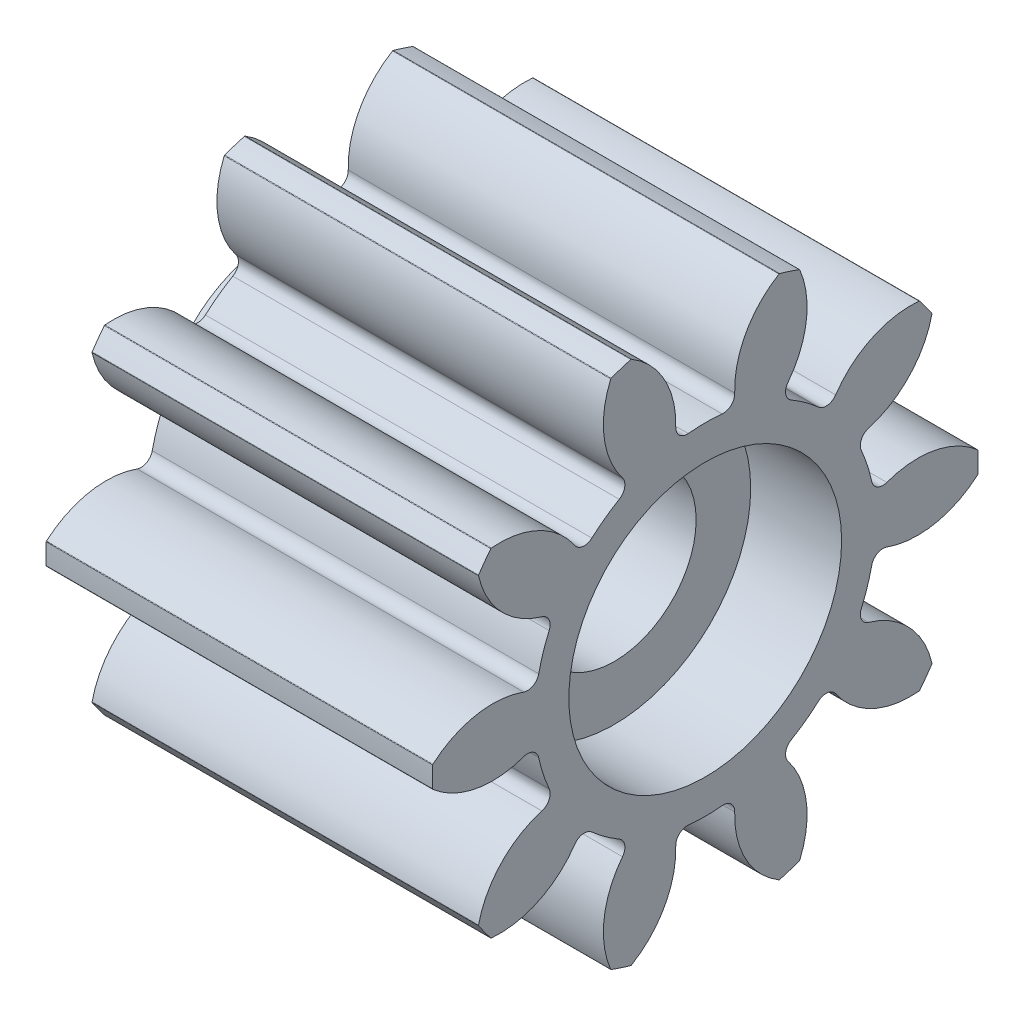
SolidWorks part; units mm, degrees
ref_plane "Plane1" through (0, 0, 0) normal (0, 0, 1) x (1, 0, 0)
ref_plane "Plane2" through (0, 0, 0) normal (0, 1, 0) x (1, 0, 0)
ref_plane "Plane3" through (0, 0, 0) normal (1, 0, 0) x (0, 0, -1)
sketch "HoldingSke" plane through (0, 0, 0) normal (0, 1, 0) x (1, 0, 0)
  line L0 (0, 0) -> (0.9848, -0.1736)
  line L1 (-15, 0) -> (100, 0) construction
  line L2 (0, 0) -> (-2.1039, 2.3779)
  line L3 (0, 0) -> (-11.863, 4.5341)
  line L4 (0, 0) -> (8.5048, 1.4996)
  line L5 (0, 0) -> (-46.8476, -17.4728)
  line L6 (0, 0) -> (-8.2896, -5.593)
  line L7 (-2.1039, 2.3779) -> (8.6586, 51.2059)
  line L8 (-76.2, 54.61) -> (-75.7, 54.61)
  line L9 (-67.7845, 28.3722) -> (-49.3413, 33.142)
  line L10 (-76.2, 71.12) -> (104.1128, 71.12)
  line L11 (0, 0) -> (-10, 0)
  line L12 (-76.2, 101.6) -> (-76.162, 101.6)
  line L13 (24.9733, 27.94) -> (52.9518, 28.4284)
  line L14 (24.9733, 27.94) -> (24.9743, 27.94)
  line L15 (24.9733, 27.94) -> (100.4006, 29.5858)
  line L16 (-63.627, -1) -> (-12.827, -1)
  circle A0 centre (0, 0) radius 1.5
  circle A1 centre (0, 0) radius 3.749
  circle A2 centre (0, 0) radius 37.5
  circle A3 centre (0, 0) radius 1.5
  dimension "Num_teeth" = 10
  dimension "Pitch_radius" = 180.3128
  dimension "Width" = 10
sketch "BasProSke" plane through (0, 0, 0) normal (0, 1, 0) x (1, 0, 0)
  line L0 (-10, 0) -> (60, 0) construction
  line L1 (0, 0) -> (0, 6)
  line L2 (0, 0) -> (8.5, 0)
  line L3 (8.5, 0) -> (8.5, 6)
  line L4 (8.5, 6) -> (0, 6)
  dimension "Thickness" = 8.5
  dimension "Diameter" = 12
revolve "Base-Revolve" add sketch "BasProSke" angle 360 about L0
sketch "TooCutSke" plane through (0, 0, 0) normal (1, 0, 0) x (0, 0, -1)
  line L1 (0, 0) -> (0, 107) construction
  line L2 (0, 0) -> (-0.8485, 4.9275) construction
  line L3 (0, 0) -> (-3.0584, 9.4126) construction
  line L4 (-0.8485, 4.9275) -> (-1.5292, 4.7063) construction
  arc A0 (0.6809, 3.6866) -> (-0.6809, 3.6866) centre (0, 0) ccw
  arc A1 (1.66, 5.7922) -> (-1.66, 5.7922) centre (0, 0) ccw
  circle A2 centre (0, 0) radius 5 construction
  circle A3 centre (0, 0) radius 4.8407 construction
  arc A4 (-0.6809, 3.6866) -> (-1.66, 5.7922) centre (-2.6471, 4.0528) ccw
  arc A5 (1.66, 5.7922) -> (0.6809, 3.6866) centre (2.6471, 4.0528) ccw
extrude "ToothCut" cut sketch "TooCutSke" along normal through all
fillet "Breaks" radius 0.02 2 edges at (4.25, 5.7745, -1.6294) (4.25, 5.7745, 1.6294) tangent propagation no
fillet "RootFillets" radius 0.251 2 edges at (4.25, 3.6866, -0.6809) (4.25, 3.6866, 0.6809)
pattern_circular "TeethCuts" count 10 every 36 about axis through (-10, 0, 0) along (1, 0, 0) of "ToothCut", "RootFillets", "Breaks"
sketch "HubNeaOneSke" plane through (0, 0, 0) normal (-1, 0, 0) x (0, 0, 1)
  circle A0 centre (0, 0) radius 3.749
  dimension "Diameter" = 7.498
extrude "HubNearOne" [suppressed] add sketch "HubNeaOneSke" along normal blind 41.5001
sketch "HubNeaBotSke" plane through (0, 0, 0) normal (-1, 0, 0) x (0, 0, 1)
  circle A0 centre (0, 0) radius 3.749
  dimension "Diameter" = 7.498
extrude "HubNearBoth" [suppressed] add sketch "HubNeaBotSke" along normal blind 20.75
ref_plane "FarPln" through (8.5, 0, 0) normal (1, 0, 0) x (0, 0, -1)
sketch "HubFarSke" plane through (8.5, 0, 0) normal (1, 0, 0) x (0, 0, -1)
  circle A0 centre (0, 0) radius 3.749
  dimension "Diameter" = 7.498
extrude "HubFar" [suppressed] add sketch "HubFarSke" along normal blind 20.75
sketch "BorSke" plane through (0, 0, 0) normal (1, 0, 0) x (0, 0, -1)
  circle A0 centre (0, 0) radius 1.8
  dimension "Diameter" = 3.6
extrude "Bore" cut sketch "BorSke" along normal mid plane 100.0001
sketch "KeySke" plane through (0, 0, 0) normal (1, 0, 0) x (0, 0, -1)
  line L0 (-0.6, 0) -> (-0.6, 2)
  line L1 (-0.6, 2) -> (0.6, 2)
  line L2 (0.6, 2) -> (0.6, 0)
  line L3 (0, 0) -> (0, 34) construction
  line L4 (-0.6, 0) -> (0.6, 0)
  dimension "Width" = 1.2
extrude "Keyway" [suppressed] cut sketch "KeySke" along normal mid plane 100.0001
pattern_circular "Keyway2" [suppressed] count 2 every 90 about axis through (-10, 0, 0) along (1, 0, 0) reverse direction yes
sketch "Sketch3" plane through (0, 0, 0) normal (-1, 0, 0) x (0, 0, 1)
  circle A0 centre (0, 0) radius 2.5
  circle A1 centre (0, 0) radius 1.8 construction
  circle A2 centre (0, 0) radius 1.8
  dimension "D1" = 5
extrude "Boss-Extrude1" add sketch "Sketch3" along normal blind 1
sketch "Sketch4" plane through (8.5, 0, 0) normal (1, 0, 0) x (0, 0, -1)
  circle A0 centre (0, 0) radius 3
  dimension "D1" = 6
extrude "Cut-Extrude2" cut sketch "Sketch4" against normal blind 2
equation "' \"Module@HoldingSke\" = 6.35"
equation "' \"Num_teeth@HoldingSke\" = 12"
equation "' \"Ap@HoldingSke\" =  20"
equation "' \"Ap@HoldingSke\" = 20"
equation "' \"Width@HoldingSke\" = 0.5 * 25.4"
equation "' \"Hub_dia@HoldingSke\"= 1 * 25.4"
equation "' \"Hub_dia@HoldingSke\" = 1 * 25.4"
equation "' \"Overall_len@HoldingSke\" = 1.0 * 25.4"
equation "' \"Bore@HoldingSke\" = 0.75 * 25.4"
equation "' \"T_dim@HoldingSke\" = 0.1 * 25.4"
equation "' \"Width@KeySke\" = 0.25 * 25.4"
equation "' \"Show_teeth@HoldingSke\" = 13"
equation "' \"Backlash@HoldingSke\" = 0.009 * 25.4"
equation "' \"Addendum_fac@HoldingSke\" = 1.0"
equation "' \"Dedendum_fac@HoldingSke\" = 1.25"
equation "' \"Dedendum_add@HoldingSke\" = 0.00005 * 25.4"
equation "' \"Clearance_fac@HoldingSke\" = 0.25"
equation "\"Pitch@HoldingSke\" = 1 / \"Module@HoldingSke\""
equation "\"Overcut_dia@TooCutSke\" = (\"Num_teeth@HoldingSke\" + 2 * \"Addendum_fac@HoldingSke\") / \"Pitch@HoldingSke\" + 0.002 * 25.4"
equation "\"Pitch_dia@TooCutSke\" = \"Num_teeth@HoldingSke\" / \"Pitch@HoldingSke\""
equation "\"Base_dia@TooCutSke\" = \"Num_teeth@HoldingSke\" / \"Pitch@HoldingSke\" * cos((\"Ap@HoldingSke\"  * 3.14159265 / 180))"
equation "\"Root_dia@TooCutSke\" = (\"Num_teeth@HoldingSke\" + 2) / \"Pitch@HoldingSke\" - 2 * (\"Addendum_fac@HoldingSke\" + \"Dedendum_fac@HoldingSke\") / \"Pitch@HoldingSke\" - \"Dedendum_add@HoldingSke\" * 2"
equation "\"Half_ang@TooCutSke\" = 180 / \"Num_teeth@HoldingSke\""
equation "\"Half_CT@TooCutSke\" = \"Num_teeth@HoldingSke\" / \"Pitch@HoldingSke\" * sin((3.14159265 / 2 / \"Num_teeth@HoldingSke\")) / 2 - 7 * \"Backlash@HoldingSke\" / 4"
equation "\"Flank_rad@TooCutSke\" = \"Num_teeth@HoldingSke\" / \"Pitch@HoldingSke\" / 5"
equation "\"Radius@RootFillets\" = \"Clearance_fac@HoldingSke\" / \"Pitch@HoldingSke\" + \"Dedendum_add@HoldingSke\""
equation "\"Break_rad@Breaks\" = 0.02 / \"Pitch@HoldingSke\""
equation "\"Thickness@HoldingSke\" = \"Width@HoldingSke\""
equation "\"OAL@HoldingSke\" = \"Thickness@HoldingSke\""
equation "\"MHD@HoldingSke\" = (\"Num_teeth@HoldingSke\" + 2) / \"Pitch@HoldingSke\" - 2 * (\"Addendum_fac@HoldingSke\" + \"Dedendum_fac@HoldingSke\")  / \"Pitch@HoldingSke\" - \"Dedendum_add@HoldingSke\" * 2"
equation "\"MBD@HoldingSke\" = (\"Num_teeth@HoldingSke\" + 2) / \"Pitch@HoldingSke\" - 2 * (\"Addendum_fac@HoldingSke\" + \"Dedendum_fac@HoldingSke\")  / \"Pitch@HoldingSke\" - \"Dedendum_add@HoldingSke\" * 2 - 0.002 * 25.4"
equation "\"MHD@HoldingSke\" = ((sgn( \"MHD@HoldingSke\" - \"Hub_dia@HoldingSke\" )-1)*( \"MHD@HoldingSke\" - \"Hub_dia@HoldingSke\" ))/-2+ \"Hub_dia@HoldingSke\""
equation "\"MBD@HoldingSke\" = ((sgn( \"MBD@HoldingSke\" - \"Bore@HoldingSke\" )-1)*( \"MBD@HoldingSke\" - \"Bore@HoldingSke\" ))/-2+ \"Bore@HoldingSke\""
equation "\"OAL@HoldingSke\" = ((sgn( \"OAL@HoldingSke\" - \"Overall_len@HoldingSke\" )+1)*( \"OAL@HoldingSke\" - \"Overall_len@HoldingSke\" ))/2 + \"Overall_len@HoldingSke\" + 0.000002 * 25.4"
equation "\"Num_teeth@TeethCuts\" = int( \"Show_teeth@HoldingSke\" ) + 1"
equation "\"Num_teeth@TeethCuts\" = ((sgn( \"Num_teeth@TeethCuts\" - \"Num_teeth@HoldingSke\" )-1)*( \"Num_teeth@TeethCuts\" - \"Num_teeth@HoldingSke\" ))/-2+ \"Num_teeth@HoldingSke\""
equation "\"Num_teeth@TeethCuts\" = ((sgn( \"Num_teeth@TeethCuts\" - 2.0)+1)*( \"Num_teeth@TeethCuts\" - 2.0))/2 +2.0"
equation "\"Angle@TeethCuts\" = 360.0 / \"Num_teeth@HoldingSke\""
equation "\"Diameter@BasProSke\" = (\"Num_teeth@HoldingSke\" + 2 * \"Addendum_fac@HoldingSke\") / \"Pitch@HoldingSke\""
equation "' \"Fillet_rad@BasProSke\" =  \"Thickness@HoldingSke\" * 0.05"
equation "' \"Fillet_rad@BasProSke\" = \"Thickness@HoldingSke\" * 0.05"
equation "\"MHD@HoldingSke\" = ((sgn( \"MHD@HoldingSke\" - \"Root_dia@TooCutSke\" )-1)*( \"MHD@HoldingSke\" - \"Root_dia@TooCutSke\" ))/-2+ \"Root_dia@TooCutSke\""
equation "\"Diameter@HubNeaOneSke\" = \"MHD@HoldingSke\""
equation "\"Length@HubNearOne\" = \"OAL@HoldingSke\" - \"Thickness@BasProSke\""
equation "\"Diameter@HubNeaBotSke\" = \"MHD@HoldingSke\""
equation "\"Length@HubNearBoth\" = ( \"OAL@HoldingSke\" - \"Thickness@BasProSke\" ) / 2.0"
equation "\"Thickness@FarPln\" = \"Thickness@BasProSke\""
equation "\"Diameter@HubFarSke\" = \"MHD@HoldingSke\""
equation "\"Length@HubFar\" = ( \"OAL@HoldingSke\" - \"Thickness@BasProSke\" ) / 2.0"
equation "\"D1@Bore\" = \"OAL@HoldingSke\" * 2.0"
equation "\"D1@Keyway\" = \"OAL@HoldingSke\" * 2.0"
equation "\"Offset@KeySke\" = \"T_dim@HoldingSke\" + \"MBD@HoldingSke\" / 2.0"
